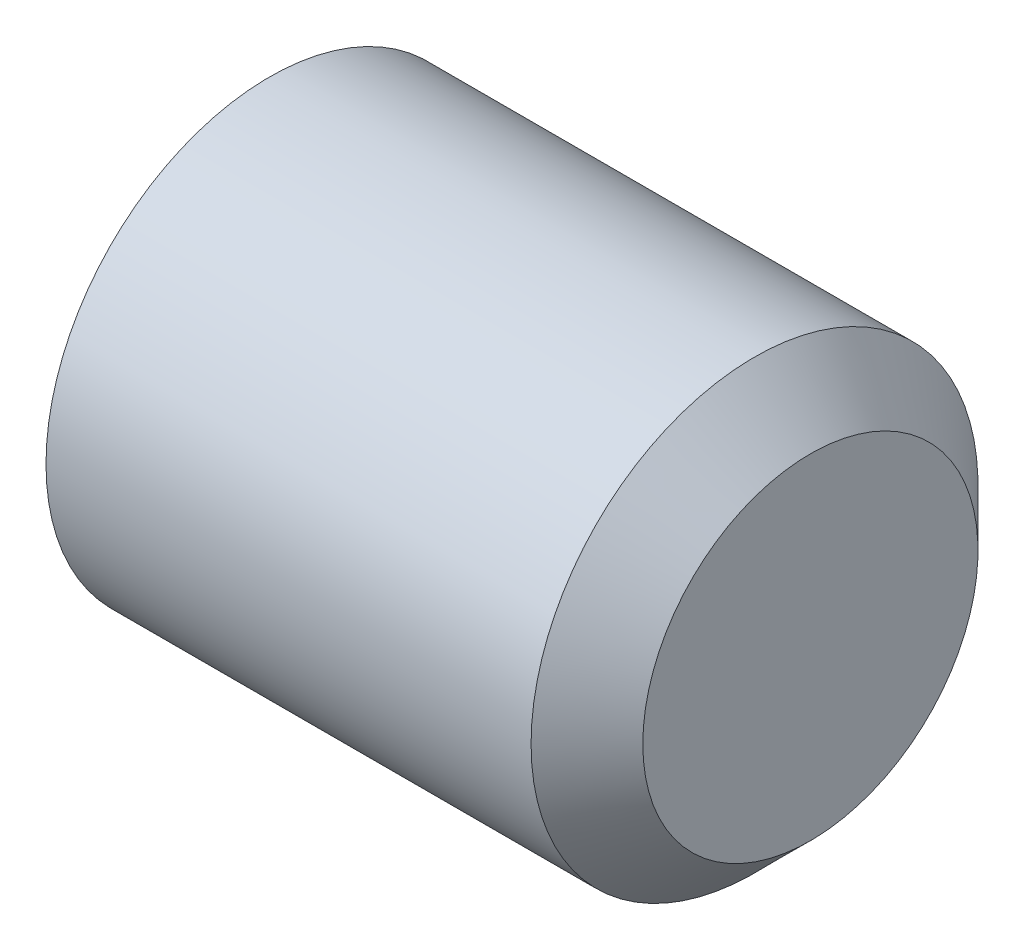
SolidWorks part; units mm, degrees
revolve "BaseBody" add sketch "BodySke" angle 360 about L5 other way angle 60
sketch "BodySke" plane through (0, 0, 0) normal (0, 0, 1) x (1, 0, 0)
  line L0 (0, 0) -> (0, 10.352)
  line L1 (0, 10.352) -> (0.9515, 12)
  line L2 (0.9515, 12) -> (27, 12)
  line L3 (27, 12) -> (30, 9)
  line L4 (30, 0) -> (0, 0)
  line L5 (-12.7, 0) -> (88.9, 0) construction
  line L6 (30, 9) -> (30, 0)
  line L7 (30, 9) -> (30, 18.525) construction
  line L8 (0, -10.352) -> (0.9515, -12) construction
  line L9 (3, 15.875) -> (3, -3.175) construction
  line L10 (27, -12) -> (30, -9) construction
  dimension "Length" = 30
  dimension "Diameter" = 24
cosmetic thread "ThreadCosmetic" [suppressed] parameters "Thread_minor"=20.704
ref_plane "Plane1" through (0, 0, 0) normal (0, 0, 1) x (1, 0, 0)
ref_plane "Plane2" through (0, 0, 0) normal (0, 1, 0) x (1, 0, 0)
ref_plane "Plane3" through (0, 0, 0) normal (1, 0, 0) x (0, 0, -1)
sketch "Sketch2" plane through (0, 0, 0) normal (-1, 0, 0) x (0, 0, 1)
  line L0 (3.4641, 6) -> (-3.4641, 6)
  line L1 (-3.4641, 6) -> (-6.9282, 0)
  line L2 (3.4641, 6) -> (6.9282, 0)
  line L3 (3.4641, -6) -> (6.9282, 0)
  line L4 (3.4641, -6) -> (-3.4641, -6)
  line L5 (-3.4641, -6) -> (-6.9282, 0)
  dimension "D2" = 6
  dimension "D3" = 6
extrude "Hex" [suppressed] cut sketch "Sketch2" against normal blind 12
sketch "Sketch4" plane through (0, 4.7709, -0.5249) normal (-1, 0, 0) x (0, 0, 1)
  line L0 (0.5249, -4.7709) -> (8.1959, -4.7709)
  line L1 (0.5249, -4.7709) -> (6.6732, -1.2211) construction
  line L2 (0.5249, -4.7709) -> (4.3604, 1.8724)
  line L3 (6.7899, -3.1774) -> (7.8687, -2.5545)
  line L4 (5.0374, -0.142) -> (6.1162, 0.4809)
  arc A0 (6.7899, -3.1774) -> (5.0374, -0.142) centre (0.5249, -4.7709) ccw
  arc A1 (8.1959, -4.7709) -> (7.8687, -2.5545) centre (0.5249, -4.7709) ccw
  arc A2 (4.3604, 1.8724) -> (6.1162, 0.4809) centre (0.5249, -4.7709) cw
  circle A3 centre (0.5249, -4.7709) radius 6.4645 construction
  circle A4 centre (0.5249, -4.7709) radius 7.671 construction
  dimension "Spline_n_dim" = 12.929
  dimension "Spline_m_dim" = 15.342
  dimension "D1" = 30
  dimension "Spline_p_dim" = 3.505
  dimension "D3" = 1.7525
extrude "Spline6" [suppressed] cut sketch "Sketch4" against normal blind 12
pattern_circular "CirPattern1" [suppressed] count 6 every 60 about axis through (-12.7, 0, 0) along (1, 0, 0)
sketch "Sketch5" plane through (0, 0.6556, 6.6316) normal (-1, 0, 0) x (0, 0, 1)
  line L0 (-6.6316, -0.6556) -> (1.0394, -0.6556)
  line L1 (-6.6316, -0.6556) -> (-1.6115, 4.3645) construction
  line L2 (-6.6316, -0.6556) -> (-6.6316, 7.0154)
  line L3 (-0.8213, 2.6763) -> (-0.1116, 3.386)
  line L4 (-3.2997, 5.1547) -> (-2.5901, 5.8644)
  line L5 (-3.2997, 5.1547) -> (-0.8213, 2.6763)
  arc A1 (1.0394, -0.6556) -> (-0.1116, 3.386) centre (-6.6316, -0.6556) ccw
  arc A2 (-6.6316, 7.0154) -> (-2.5901, 5.8644) centre (-6.6316, -0.6556) cw
  circle A3 centre (-6.6316, -0.6556) radius 6.4645 construction
  circle A4 centre (-6.6316, -0.6556) radius 7.671 construction
  dimension "Spline_n_dim" = 12.929
  dimension "Spline_m_dim" = 15.342
  dimension "Spline_p_dim" = 3.505
  dimension "D3" = 1.7525
  dimension "D1" = 45
  dimension "Spline_a_dim" = 90
extrude "Spline4" [suppressed] cut sketch "Sketch5" against normal blind 12
pattern_circular "CirPattern2" [suppressed] count 4 every 90 about axis through (-12.7, 0, 0) along (1, 0, 0)
sketch "ThdSchSke" plane through (0, 0, 0) normal (0, 0, 1) x (1, 0, 0)
  line L0 (0.9515, -10.352) -> (-0.2025, -12)
  line L1 (0.9515, -10.352) -> (2.1054, -12)
  line L2 (2.1054, -12) -> (2.1054, -15)
  line L3 (-3.175, 0) -> (5.1513, 0) construction
  line L4 (0.9515, 12) -> (0.9515, -12) construction
  line L5 (2.1054, -15) -> (-0.2025, -15)
  line L6 (-0.2025, -15) -> (-0.2025, -12)
  dimension "Thread_minor" = 20.704
  dimension "Diameter" = 24
revolve "ThreadSchematic" [suppressed] cut sketch "ThdSchSke" angle 360 about L3
pattern_linear "ThdSchPat" [suppressed]
equation "\"D2@Sketch2\" = \"Hex_size@Sketch2\" / 2"
equation "\"D3@Sketch2\" = \"Hex_size@Sketch2\" / 2"
equation "\"Thread_minor@ThreadCosmetic\" = \"Minor_dia@BodySke\""
equation "\"D1@Sketch4\" = \"Spline_a_dim@Sketch4\" / 2"
equation "\"D3@Sketch4\" = \"Spline_p_dim@Sketch4\" / 2"
equation "\"D2@CirPattern1\" = \"Spline_a_dim@Sketch4\""
equation "\"Num_teeth@CirPattern1\" = 360 / \"D2@CirPattern1\""
equation "\"Spline_a_dim@Sketch5\" = 90"
equation "\"Spline_p_dim@Sketch5\" = \"Spline_p_dim@Sketch4\""
equation "\"Spline_m_dim@Sketch5\" = \"Spline_m_dim@Sketch4\""
equation "\"Spline_n_dim@Sketch5\" = \"Spline_n_dim@Sketch4\""
equation "\"D1@Sketch5\" = \"Spline_a_dim@Sketch5\" / 2"
equation "\"D3@Sketch5\" = \"Spline_p_dim@Sketch5\" / 2"
equation "\"Key_eng@Spline4\" = \"Key_eng@Spline6\""
equation "\"Thread_minor@ThdSchSke\" = \"Thread_minor@ThreadCosmetic\""
equation "\"Diameter@ThdSchSke\" = \"Diameter@BodySke\""
equation "\"Overcut@ThdSchSke\" = \"Diameter@BodySke\" * 1.25"
equation "\"Num_threads@ThdSchPat\" = int( (\"Length@BodySke\" - ( ( ( \"Diameter@BodySke\" - \"Minor_dia@BodySke\" ) * 0.5 ) / tan( \"Drive_ch_ang@BodySke\" * 0.017453292 ) ) - ( ( ( \"Diameter@BodySke\" - \"Cup_dia@BodySke\" ) * 0.5 ) * tan( \"Cup_nose_ang@BodySke\" * 0.017453292 ) ) ) / \"Advance@BodySke\" + 0.999 )  + 1"
equation "\"Advance@ThdSchPat\" = (\"Length@BodySke\" - ( ( ( \"Diameter@BodySke\" - \"Minor_dia@BodySke\" ) * 0.5 ) / tan( \"Drive_ch_ang@BodySke\" * 0.017453292 ) ) - ( ( ( \"Diameter@BodySke\" - \"Cup_dia@BodySke\" ) * 0.5 ) * tan( \"Cup_nose_ang@BodySke\" * 0.017453292 ) ) ) /  (\"Num_threads@ThdSchPat\" - 1) 'relax it"
equation "' \"Num_threads@ThdSchPat\" = \"Num_threads@ThdSchPat\" - sgn( \"Num_threads@ThdSchPat\" - 1) '---chamfered tips only---"
